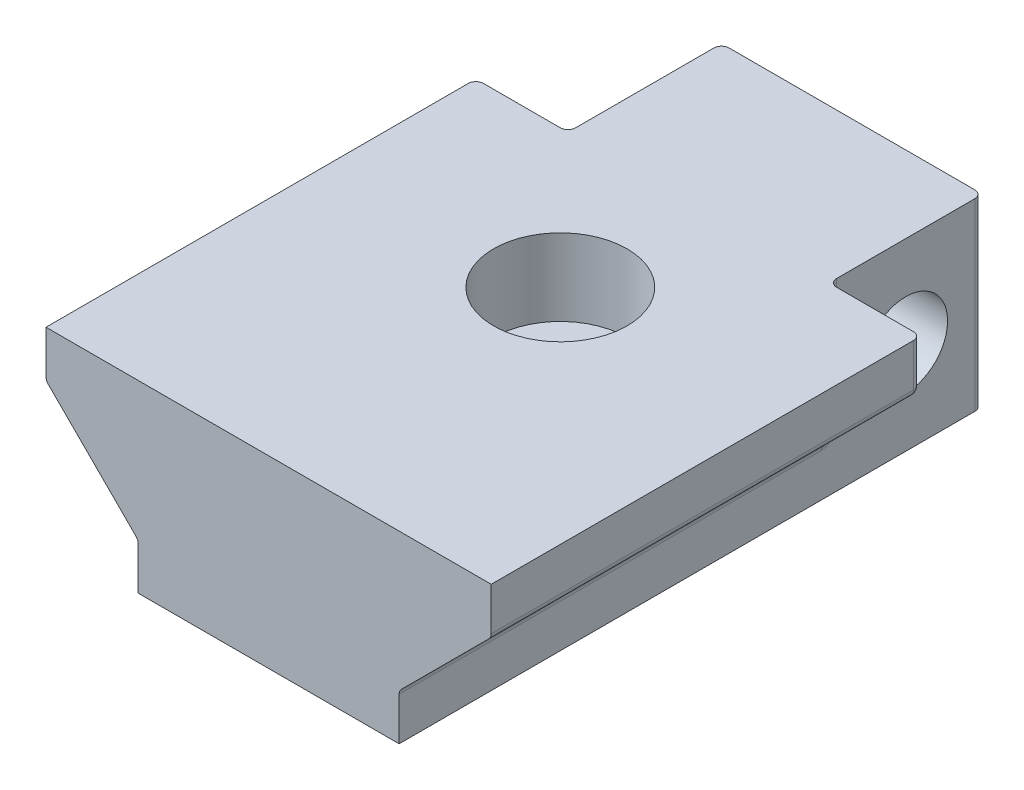
SolidWorks part; units mm, degrees
material "ABS"
ref_plane "Front Plane" through (0, 0, 0) normal (0, 0, 1) x (1, 0, 0)
ref_plane "Top Plane" through (0, 0, 0) normal (0, 1, 0) x (1, 0, 0)
ref_plane "Right Plane" through (0, 0, 0) normal (1, 0, 0) x (0, 0, -1)
sketch "Sketch1" plane through (0, 0, 0) normal (0, 0, 1) x (1, 0, 0)
  line L0 (0, 0) -> (0, 12) construction
  line L1 (-14.5, 12) -> (-14.5, 9)
  line L2 (-14.5, 9) -> (-8.5, 3)
  line L3 (-8.5, 3) -> (-8.5, 0)
  line L4 (8.5, 3) -> (8.5, 0)
  line L5 (14.5, 9) -> (8.5, 3)
  line L6 (14.5, 12) -> (14.5, 9)
  line L7 (-14.5, 12) -> (14.5, 12)
  line L8 (-8.5, 0) -> (8.5, 0)
  dimension "D1" = 12
  dimension "D2" = 3
  dimension "D3" = 45
  dimension "D4" = 17
extrude "Dovetail Body" add sketch "Sketch1" along normal mid plane 38
sketch "Sketch9" plane through (0, 0, -19) normal (0, 0, -1) x (-1, 0, 0)
  line L0 (0, 12) -> (0, 0) construction
  line L1 (-14.5, 12) -> (-8.5, 12)
  line L2 (-14.5, 12) -> (-14.5, 0)
  line L3 (-14.5, 0) -> (-8.5, 0)
  line L4 (-8.5, 12) -> (-8.5, 0)
  line L5 (-14.5, 12) -> (14.5, 12) construction
  line L6 (8.5, 0) -> (-8.5, 0) construction
  line L7 (8.5, 12) -> (8.5, 0)
  line L8 (14.5, 0) -> (8.5, 0)
  line L9 (14.5, 12) -> (14.5, 0)
  line L10 (14.5, 12) -> (8.5, 12)
extrude "Bolt Clearance" cut sketch "Sketch9" against normal blind 10
sketch "Sketch10" plane through (8.5, 0, 0) normal (1, 0, 0) x (0, 0, -1)
  line L0 (14, 12) -> (14, 0) construction
  line L1 (9, 12) -> (19, 12) construction
  line L2 (-19, 0) -> (19, 0) construction
  circle A0 centre (14, 6) radius 2.725
  dimension "D1" = 5.45
extrude "Bolt Insert" cut sketch "Sketch10" against normal through all
sketch "Sketch11" plane through (0, 0, 0) normal (0, -1, 0) x (1, 0, 0)
  line L7 (8.5, -16.725) -> (8.5, -11.275) construction
  line L8 (8.5, -16.725) -> (8.5, -11.275) construction
  circle A0 centre (0, 0) radius 2.725
  dimension "D1" = 5.45
extrude "M5 Hole" cut sketch "Sketch11" against normal through all
sketch "Sketch12" plane through (0, 12, 0) normal (0, -1, 0) x (1, 0, 0)
  circle A0 centre (0, 0) radius 4.35
  dimension "D1" = 8.7
extrude "M5 Countersink" cut sketch "Sketch12" along normal blind 5
fillet "Contouring" radius 0.5 12 edges at (8.5, 7.5, -9) (-8.5, 7.5, -9) (8.5, 3, 5) (-8.5, 3, 5) (-14.5, 9, 5) (14.5, 9, 5) (-11.5, 6, -9) (-14.5, 10.5, -9) (-8.5, 6, -19) (8.5, 6, -19) (11.5, 6, -9) (14.5, 10.5, -9)
equation "\"width keep\"= 3"
equation "\"dovetail height\"= 12"
equation "\"dovetail angle\"= 45"
equation "\"dovetail width\"= 17"
equation "\"D1@Sketch1\"=\"dovetail height\""
equation "\"D2@Sketch1\"=\"width keep\""
equation "\"D3@Sketch1\"=\"dovetail angle\""
equation "\"D4@Sketch1\"=\"dovetail width\""
equation "\"dovetail length\"= 38"
equation "\"D1@Dovetail Body\" = \"dovetail length\""
equation "\"print free\"= 0.45"
equation "\"print fit\"= 0.2"
equation "\"D1@Sketch11\"= 5.00mm+\"print free\""
equation "\"D1@Sketch12\"= 8.50mm+\"print fit\""
equation "\"D1@Sketch10\"=5+\"print free\""
